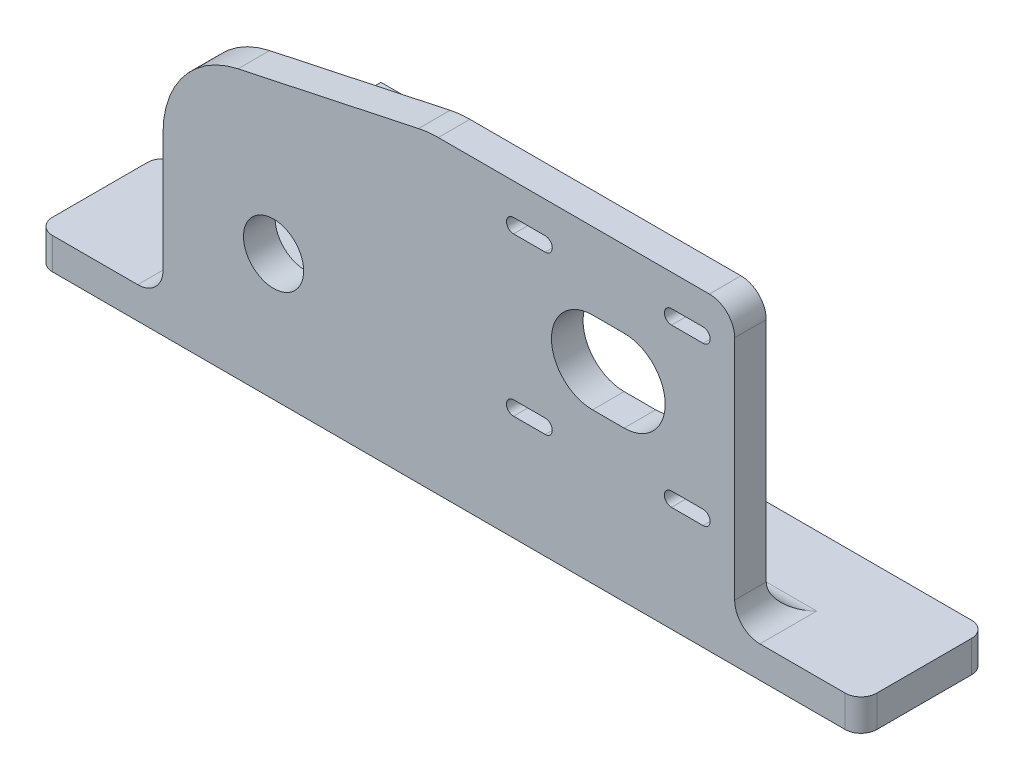
SolidWorks part; units mm, degrees
ref_plane "Front Plane" through (0, 0, 0) normal (0, 0, 1) x (1, 0, 0)
ref_plane "Top Plane" through (0, 0, 0) normal (0, 1, 0) x (1, 0, 0)
ref_plane "Right Plane" through (0, 0, 0) normal (1, 0, 0) x (0, 0, -1)
sketch "Sketch1" plane through (0, 0, 0) normal (0, 0, 1) x (1, 0, 0)
  line L0 (146, 57.9382) -> (146, -30)
  line L1 (-35, -30) -> (146, -30)
  line L8 (101, 20.6882) -> (111, 20.6882) construction
  line L10 (146, 57.9382) -> (49, 57.9382)
  line L13 (-35, 40) -> (-35, -30)
  line L28 (81, -4.3118) -> (131, -4.3118) construction
  line L32 (81, -4.3118) -> (81, 45.6882) construction
  line L35 (81, 45.6882) -> (131, 45.6882) construction
  line L38 (131, -4.3118) -> (131, 45.6882) construction
  line L41 (81, -4.3118) -> (131, 45.6882) construction
  line L42 (81, 45.6882) -> (131, -4.3118) construction
  line L43 (101, 33.6882) -> (111, 33.6882)
  line L44 (101, 7.6882) -> (111, 7.6882)
  line L45 (86, 45.6882) -> (76, 45.6882) construction
  line L46 (86, 43.4382) -> (76, 43.4382)
  line L47 (86, 47.9382) -> (76, 47.9382)
  line L48 (86, -4.3118) -> (76, -4.3118) construction
  line L49 (86, -6.5618) -> (76, -6.5618)
  line L50 (86, -2.0618) -> (76, -2.0618)
  line L51 (126, -4.3118) -> (136, -4.3118) construction
  line L52 (126, -2.0618) -> (136, -2.0618)
  line L53 (126, -6.5618) -> (136, -6.5618)
  line L54 (126, 45.6882) -> (136, 45.6882) construction
  line L55 (126, 47.9382) -> (136, 47.9382)
  line L56 (126, 43.4382) -> (136, 43.4382)
  line L57 (0, 0) -> (106, 20.6882) construction
  line L58 (-35, 40) -> (49, 57.9382)
  circle A0 centre (0, 0) radius 4.7625 construction
  circle A1 centre (0, 0) radius 48.26 construction
  circle A17 centre (0, 0) radius 9.525
  arc A32 (101, 33.6882) -> (101, 7.6882) centre (101, 20.6882) ccw
  arc A33 (111, 7.6882) -> (111, 33.6882) centre (111, 20.6882) ccw
  arc A34 (86, 43.4382) -> (86, 47.9382) centre (86, 45.6882) ccw
  arc A35 (76, 47.9382) -> (76, 43.4382) centre (76, 45.6882) ccw
  arc A36 (86, -6.5618) -> (86, -2.0618) centre (86, -4.3118) ccw
  arc A37 (76, -2.0618) -> (76, -6.5618) centre (76, -4.3118) ccw
  arc A38 (126, -2.0618) -> (126, -6.5618) centre (126, -4.3118) ccw
  arc A39 (136, -6.5618) -> (136, -2.0618) centre (136, -4.3118) ccw
  arc A40 (126, 47.9382) -> (126, 43.4382) centre (126, 45.6882) ccw
  arc A41 (136, 43.4382) -> (136, 47.9382) centre (136, 45.6882) ccw
  point P4 (106, 20.6882)
  point P11 (106, 20.6882)
  point P18 (81, 45.6882)
  point P23 (0, 0)
  point P28 (81, -4.3118)
  point P35 (131, -4.3118)
  point P43 (131, 45.6882)
  dimension "D1" = 9.525
  dimension "D2" = 96.52
  dimension "D3" = 50
  dimension "D4" = 13
  dimension "D6" = 10
  dimension "D12" = 181
  dimension "D13" = 19.05
  dimension "D7" = 2.25
  dimension "D5" = 10
  dimension "D8" = 10
  dimension "D9" = 35
  dimension "D10" = 15
  dimension "D11" = 108
  dimension "D14" = 97
  dimension "D15" = 70
  dimension "D16" = 30
extrude "Boss-Extrude1" add sketch "Sketch1" along normal blind 10
sketch "Sketch2" plane through (0, -30, 0) normal (0, -1, 0) x (1, 0, 0)
  line L1 (-35, 10) -> (146, 10)
  line L2 (-35, 10) -> (-35, -90)
  line L3 (-35, -90) -> (146, -90)
  line L4 (146, 10) -> (146, -90)
  line L5 (146, 10) -> (146, 0) construction
  dimension "D1" = 100
extrude "Boss-Extrude2" add sketch "Sketch2" along normal blind 10
ref_plane "Plane1" through (0, 0, -55) normal (0, 0, 1) x (1, 0, 0)
sketch "Sketch3" plane through (0, 0, -55) normal (0, 0, 1) x (1, 0, 0)
  line L0 (0, 74.8076) -> (0, -74.8076) construction
  line L1 (-31, 0) -> (-31, -40)
  line L2 (-35, -40) -> (146, -40) construction
  line L3 (-31, -40) -> (31, -40)
  line L4 (31, -40) -> (31, 0)
  line L5 (31, 0) -> (19, 0)
  line L6 (-19, 0) -> (-31, 0)
  arc A0 (-19, 0) -> (19, 0) centre (0, 0) ccw
  arc A1 (-31, 0) -> (31, 0) centre (0, 0) ccw construction
  point P4 (0, -19)
  point P5 (0, 0)
  dimension "D1" = 12
  dimension "D2" = 19
  dimension "D3" = 21
extrude "Boss-Extrude3" add sketch "Sketch3" along normal blind 18
sketch "Sketch4" plane through (0, 0, 0) normal (0, 1, 0) x (1, 0, 0)
  line L0 (-25, 55) -> (-25, 37) construction
  line L1 (-19, 55) -> (-31, 55) construction
  line L2 (-19, 37) -> (-31, 37) construction
  line L3 (-19, 46) -> (-31, 46) construction
  line L4 (-19, 37) -> (-19, 55) construction
  line L5 (-31, 55) -> (-31, 37) construction
  line L6 (25, 37) -> (25, 55) construction
  line L7 (31, 37) -> (19, 37) construction
  line L8 (31, 55) -> (19, 55) construction
  line L9 (31, 46) -> (19, 46) construction
  line L10 (31, 37) -> (31, 55) construction
  line L11 (19, 37) -> (19, 55) construction
  circle A0 centre (-25, 46) radius 2
  circle A1 centre (25, 46) radius 2
  dimension "D1" = 4
  dimension "D2" = 4
extrude "Cut-Extrude1" cut sketch "Sketch4" against normal up to surface (30 mm away) up to face at (0, -30, -46)
ref_plane "Plane2" through (0, -6, 0) normal (0, 1, 0) x (1, 0, 0)
sketch "Sketch5" plane through (0, -6, 0) normal (0, 1, 0) x (1, 0, 0)
  circle A0 centre (25, 46) radius 4
  circle A1 centre (-25, 46) radius 4
  dimension "D1" = 8
  dimension "D2" = 8
extrude "Cut-Extrude2" cut sketch "Sketch5" against normal blind 20
ref_plane "Plane3" through (31, 0, -37) normal (0, 1, 0) x (1, 0, 0)
sketch "Sketch8" plane through (0, 0, -37) normal (0, 0, 1) x (1, 0, 0)
  line L0 (31, -30) -> (31, 0) construction
  line L1 (-31, 0) -> (31, 0)
  line L2 (-31, 0) -> (-31, -1)
  line L3 (-31, -1) -> (31, -1)
  line L4 (31, 0) -> (31, -1)
  dimension "D1" = 1
extrude "Cut-Extrude4" cut sketch "Sketch8" against normal up to next
sketch "Sketch6" plane through (0, 0, -55) normal (0, 0, -1) x (-1, 0, 0)
  line L0 (31, -1) -> (20, -21)
  line L6 (-31, -1) -> (-20, -21)
  line L9 (-20, -21) -> (-20, -30)
  line L10 (35, -30) -> (-146, -30) construction
  line L11 (-20, -30) -> (-31, -30)
  line L12 (-31, -30) -> (-31, -1)
  line L13 (20, -21) -> (20, -30)
  line L14 (-31, -30) -> (31, -30) construction
  line L15 (20, -30) -> (31, -30)
  line L16 (31, -30) -> (31, -1)
  line L17 (35, -40) -> (-146, -40) construction
  dimension "D1" = 19
  dimension "D2" = 40
extrude "Cut-Extrude3" cut sketch "Sketch6" against normal up to next
fillet "Fillet1" radius 5 4 edges at (-20, -21, -46) (20, -21, -46) (20, -30, -46) (-20, -30, -46)
sketch "Sketch9" plane through (0, -40, 0) normal (0, -1, 0) x (1, 0, 0)
  line L1 (-35, 10) -> (-75, 10)
  line L2 (-35, 10) -> (-35, -30)
  line L3 (-35, -30) -> (-75, -30)
  line L4 (-75, 10) -> (-75, -30)
  line L5 (146, 10) -> (186, 10)
  line L6 (146, 10) -> (146, -30)
  line L7 (146, -30) -> (186, -30)
  line L8 (186, 10) -> (186, -30)
  dimension "D1" = 40
extrude "Boss-Extrude5" add sketch "Sketch9" against normal blind 10
sketch "Sketch10" plane through (0, -30, 0) normal (0, 1, 0) x (1, 0, 0)
  line L0 (25, 37) -> (-25, 37) construction
  line L1 (25, 37) -> (-25, 37) construction
  line L2 (25, 55) -> (25, 37) construction
  line L3 (25, 55) -> (-25, 55) construction
  line L4 (-25, 37) -> (-25, 55) construction
  line L5 (25, 55) -> (25, 37) construction
  line L6 (25, 55) -> (-25, 55) construction
  line L7 (-25, 37) -> (-25, 55) construction
  line L8 (30, 30) -> (30, 60)
  line L11 (30, 30) -> (146, 30)
  line L12 (-35, 90) -> (-35, 30)
  line L13 (-35, 30) -> (-75, 30)
  line L14 (-75, 30) -> (-75, -10)
  line L15 (-75, -10) -> (-35, -10)
  line L16 (-35, -10) -> (-35, 0)
  line L17 (-35, 0) -> (146, 0)
  line L18 (146, 0) -> (146, -10)
  line L19 (146, -10) -> (186, -10)
  line L20 (186, -10) -> (186, 30)
  line L21 (186, 30) -> (146, 30)
  line L22 (146, 30) -> (146, 90)
  line L23 (146, 90) -> (-35, 90)
  line L24 (-35, 90) -> (-35, 30) construction
  line L25 (-35, 30) -> (-75, 30) construction
  line L26 (-75, 30) -> (-75, -10) construction
  line L27 (-75, -10) -> (-35, -10) construction
  line L28 (-35, -10) -> (-35, 0) construction
  line L29 (-35, 0) -> (146, 0) construction
  line L30 (146, 0) -> (146, -10) construction
  line L31 (146, -10) -> (186, -10) construction
  line L32 (186, -10) -> (186, 30) construction
  line L33 (186, 30) -> (146, 30) construction
  line L34 (146, 30) -> (146, 90) construction
  line L35 (146, 90) -> (-35, 90) construction
  line L36 (146, 30) -> (146, 90)
  line L37 (146, 90) -> (-35, 90)
  line L38 (-35, 90) -> (-35, 60)
  line L39 (30, 60) -> (-35, 60)
  line L40 (-35, 30) -> (-35, 90) construction
  dimension "D2" = 5
  dimension "D3" = 5
  dimension "D1" = 0
extrude "Cut-Extrude6" cut sketch "Sketch10" against normal through all
fillet "Fillet2" radius 5 8 edges at (-35, -35, -30) (-75, -35, -30) (-75, -35, 10) (186, -35, 10) (186, -35, -30) (-35, -35, -60) (30, -35, -30) (30, -35, -60)
fillet "Fillet3" radius 5 2 edges at (0, -30, -55) (0, -30, -37)
fillet "Fillet4" radius 8 4 edges at (-35, -30, 5) (146, -30, 5) (55.5, -30, 0) (146, 57.9382, 5)
fillet "Fillet5" radius 30 2 edges at (-35, 40, 5) (49, 57.9382, 5)
